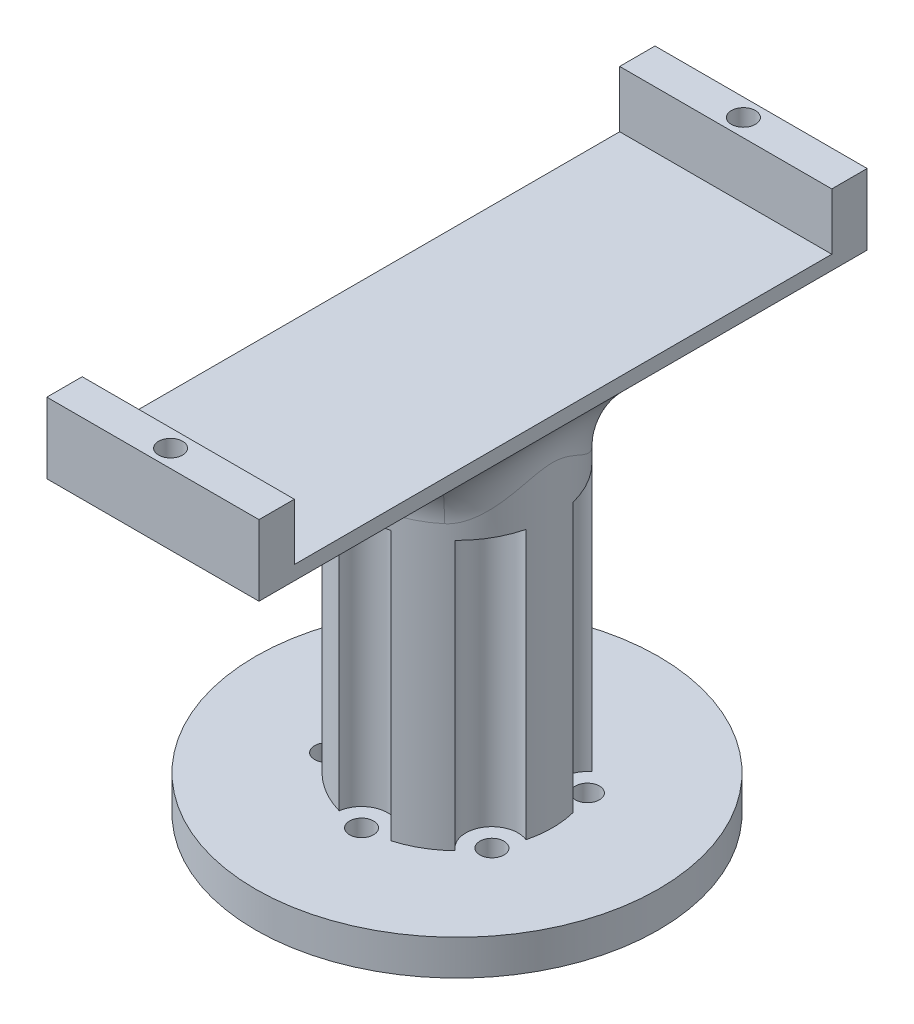
SolidWorks part; units mm, degrees
ref_plane "前视基准面" through (0, 0, 0) normal (0, 0, 1) x (1, 0, 0)
ref_plane "上视基准面" through (0, 0, 0) normal (0, 1, 0) x (1, 0, 0)
ref_plane "右视基准面" through (0, 0, 0) normal (1, 0, 0) x (0, 0, -1)
sketch "草图1" plane through (0, 0, 0) normal (0, 1, 0) x (1, 0, 0)
  circle A0 centre (0, 0) radius 13.5 construction
  circle A1 centre (0, 0) radius 28.5
  circle A2 centre (0, 13.5) radius 1.7
  circle A3 centre (11.6913, 6.75) radius 1.7
  circle A4 centre (11.6913, -6.75) radius 1.7
  circle A5 centre (0, -13.5) radius 1.7
  circle A6 centre (-11.6913, -6.75) radius 1.7
  circle A7 centre (-11.6913, 6.75) radius 1.7
  point P18 (0, 0)
  dimension "D1" = 27
  dimension "D2" = 57
  dimension "D3" = 3.4
  dimension "D4" = 6
extrude "凸台-拉伸1" add sketch "草图1" along normal blind 5
sketch "草图2" plane through (0, 5, 0) normal (0, 1, 0) x (1, 0, 0)
  circle A0 centre (0, 0) radius 13.5
  dimension "D1" = 27
extrude "凸台-拉伸2" add sketch "草图2" along normal blind 50
sketch "草图3" plane through (0, 55, 0) normal (0, 1, 0) x (1, 0, 0)
  line L1 (-15, 43) -> (15, 43)
  line L2 (-15, 43) -> (-15, -43)
  line L3 (-15, -43) -> (15, -43)
  line L4 (15, 43) -> (15, -43)
  line L5 (-15, 43) -> (15, -43) construction
  line L6 (-15, -43) -> (15, 43) construction
  point P0 (0, 0)
  dimension "D1" = 86
  dimension "D2" = 30
extrude "凸台-拉伸3" add sketch "草图3" along normal blind 10
sketch "草图4" plane through (0, 65, 0) normal (0, 1, 0) x (1, 0, 0)
  line L1 (-49.898, -38) -> (49.898, -38)
  line L2 (-49.898, -38) -> (-49.898, 38)
  line L3 (-49.898, 38) -> (49.898, 38)
  line L4 (49.898, -38) -> (49.898, 38)
  line L5 (-49.898, -38) -> (49.898, 38) construction
  line L6 (-49.898, 38) -> (49.898, -38) construction
  point P0 (0, 0)
  dimension "D1" = 76
extrude "切除-拉伸1" cut sketch "草图4" against normal blind 8
sketch "草图5" plane through (0, 65, 0) normal (0, 1, 0) x (1, 0, 0)
  line L0 (0, 48.0005) -> (0, -50.7184) construction
  line L1 (-15, -43) -> (15, -43) construction
  line L2 (15, 43) -> (-15, 43) construction
  circle A1 centre (0, 40.5) radius 1.7
  circle A2 centre (0, -40.5) radius 1.7
  dimension "D1" = 2.5
  dimension "D2" = 3.4
  dimension "D3" = 3.4
  dimension "D4" = 2.5
extrude "切除-拉伸2" cut sketch "草图5" against normal blind 18
fillet "圆角1" radius 10 1 edges at (0, 55, 13.5)
sketch "草图6" plane through (0, 5, 0) normal (0, 1, 0) x (1, 0, 0)
  circle A0 centre (-11.6913, -6.75) radius 3.7
  arc A1 (-12.447, -5.2272) -> (-10.7503, -8.1658) centre (0, 0) ccw construction
  circle A2 centre (-11.6913, 6.75) radius 3.7
  circle A3 centre (0, 13.5) radius 3.7
  circle A4 centre (11.6913, 6.75) radius 3.7
  circle A5 centre (11.6913, -6.75) radius 3.7
  circle A6 centre (0, -13.5) radius 3.7
  point P17 (0, 0)
  dimension "D1" = 7.4
  dimension "D2" = 6
extrude "切除-拉伸3" cut sketch "草图6" along normal blind 38
